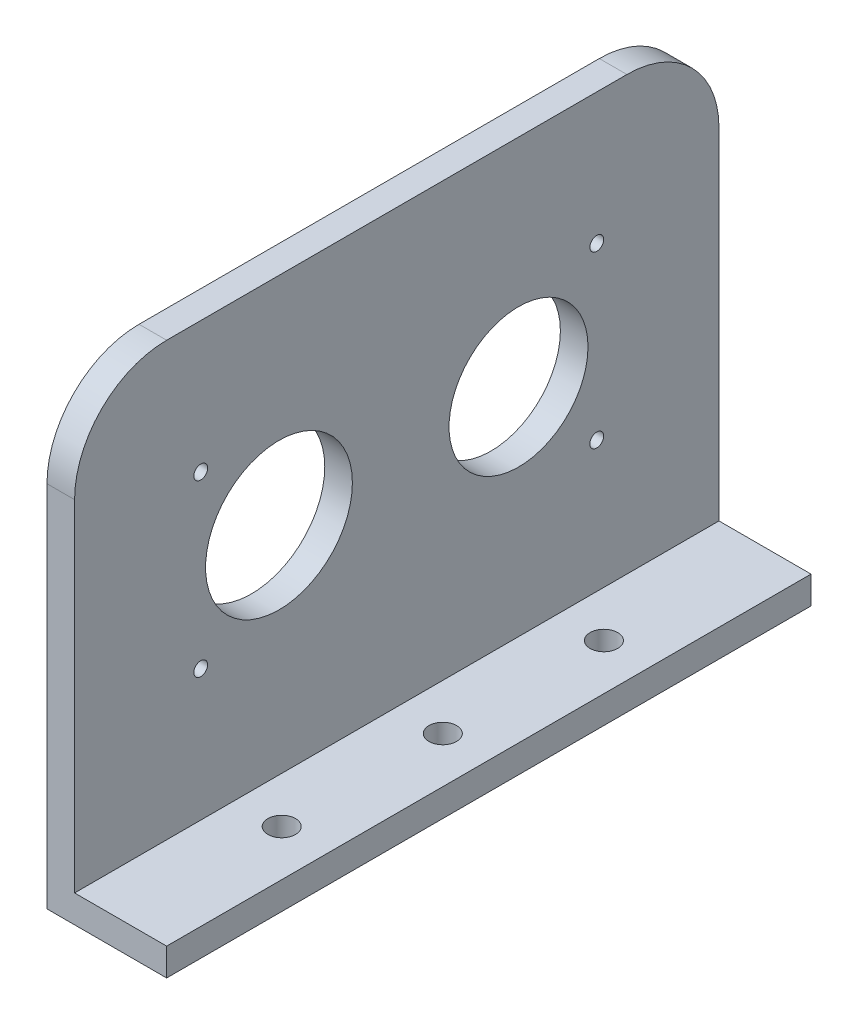
SolidWorks part; units mm, degrees
ref_plane "Front Plane" through (0, 0, 0) normal (0, 0, 1) x (1, 0, 0)
ref_plane "Top Plane" through (0, 0, 0) normal (0, 1, 0) x (1, 0, 0)
ref_plane "Right Plane" through (0, 0, 0) normal (1, 0, 0) x (0, 0, -1)
sketch "Sketch1" plane through (0, 0, 0) normal (0, 0, 1) x (1, 0, 0)
  line L0 (0, 0) -> (0, 3)
  line L1 (0, 3) -> (-10, 3)
  line L2 (-10, 3) -> (-10, 50)
  line L3 (-10, 50) -> (-13, 50)
  line L4 (-13, 50) -> (-13, 0)
  line L5 (-13, 0) -> (0, 0)
  dimension "D1" = 50
  dimension "D2" = 3
  dimension "D3" = 3
  dimension "D4" = 10
extrude "Boss-Extrude1" add sketch "Sketch1" along normal blind 70 contours L4 L5 L0 L1 L2 L3
sketch "Sketch2" plane through (-10, 0, 0) normal (1, 0, 0) x (0, 0, -1)
  line L0 (-31.1498, 39) -> (-31.1498, 50) construction
  line L1 (-60, 39) -> (-10, 39)
  line L2 (-60, 39) -> (-60, 14)
  line L3 (-60, 14) -> (-10, 14)
  line L4 (-10, 39) -> (-10, 14)
  line L5 (-70, 50) -> (0, 50) construction
  line L6 (-26.3251, 14) -> (-26.3251, 3) construction
  line L7 (-70, 3) -> (0, 3) construction
  line L8 (-10, 28.025) -> (0, 28.025) construction
  line L9 (0, 3) -> (0, 50) construction
  line L10 (-60, 26.6465) -> (-70, 26.6465) construction
  line L11 (-70, 3) -> (-70, 50) construction
  line L13 (-39.8225, 26.5) -> (-29.3225, 26.5) construction
  line L14 (-14.2275, 26.5) -> (-10, 26.5) construction
  line L15 (-55.7725, 26.5) -> (-60, 26.5) construction
  circle A0 centre (-47.7975, 26.5) radius 7.975
  circle A1 centre (-21.775, 26.5) radius 7.5475
  point P30 (0, 0)
  point P31 (0, 0)
  dimension "D3" = 15.95
  dimension "D4" = 15.095
  dimension "D1" = 50
  dimension "D2" = 25
  dimension "D5" = 10.5
  dimension "D6" = 26.0225
extrude "Cut-Extrude9" cut sketch "Sketch2" against normal through all contours A0
extrude "Cut-Extrude10" cut sketch "Sketch2<12>" against normal through all contours A1
sketch "Sketch2<12>" plane through (-10, 0, 0) normal (1, 0, 0) x (0, 0, -1) same geometry as "Sketch2"
fillet "Fillet1" radius 10 1 edges at (-11.5, 50, 70) type face fillet first side face at (-11.5, 50, 35) second side face at (-7.6667, 17.6667, 70)
fillet "Fillet2" radius 10 1 edges at (-11.5, 50, 0) type face fillet first side face at (-11.5, 50, 30) second side face at (-7.6667, 17.6667, 0)
sketch "Sketch3" plane through (0, 3, 0) normal (0, 1, 0) x (1, 0, 0)
  line L0 (-5, 0) -> (-5, -70) construction
  line L1 (0, 0) -> (-10, 0) construction
  line L2 (0, -70) -> (-10, -70) construction
  circle A0 centre (-5, -35) radius 1.5
  circle A1 centre (-5, -52.5) radius 1.5
  circle A2 centre (-5, -17.5) radius 1.5
  dimension "D1" = 17.5
  dimension "D2" = 17.5
  dimension "D3" = 3
  dimension "D4" = 17.5
  dimension "D5" = 3
  dimension "D6" = 3
extrude "Cut-Extrude11" cut sketch "Sketch3" against normal through all
sketch "Sketch4" plane through (-13, 0, 0) normal (-1, 0, 0) x (0, 0, 1)
  circle A0 centre (56.2975, 35.75) radius 0.75
  circle A1 centre (13.275, 35.75) radius 0.75
  circle A2 centre (13.275, 17.25) radius 0.75
  circle A3 centre (56.2975, 17.25) radius 0.75
  circle A4 centre (21.775, 26.5) radius 7.5475 construction
  circle A5 centre (47.7975, 26.5) radius 7.975 construction
  point P8 (0, 0)
  point P11 (0, 0)
  point P12 (0, 0)
  point P13 (0, 0)
  dimension "D1" = 9.25
  dimension "D5" = 8.5
  dimension "D6" = 8.5
  dimension "D7" = 8.5
  dimension "D8" = 8.5
  dimension "D9" = 1.5
  dimension "D10" = 1.5
  dimension "D11" = 1.5
  dimension "D12" = 1.5
  dimension "D2" = 9.25
  dimension "D3" = 9.25
  dimension "D4" = 9.25
extrude "Cut-Extrude12" cut sketch "Sketch4" against normal through all
